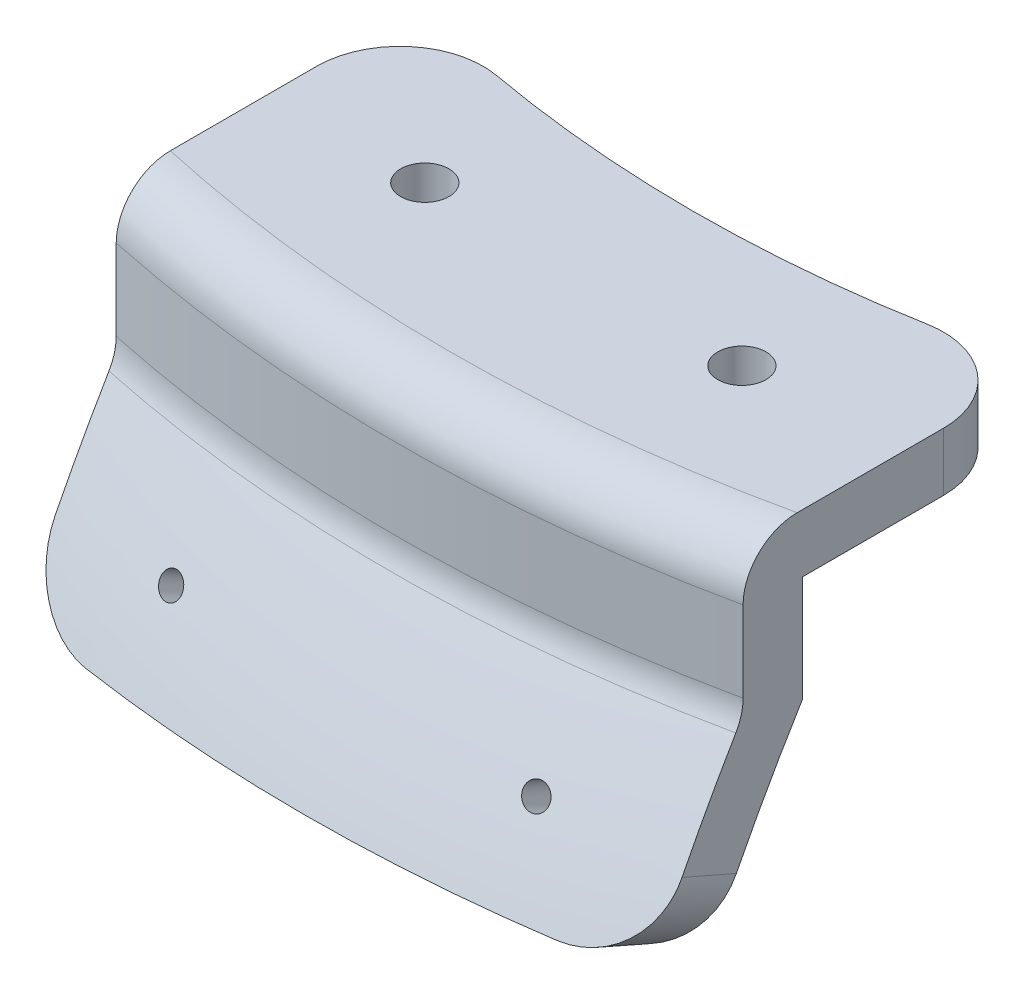
SolidWorks part; units mm, degrees
material "Polyether Polyol"
ref_plane "Front Plane" through (0, 0, 0) normal (0, 0, 1) x (1, 0, 0)
ref_plane "Top Plane" through (0, 0, 0) normal (0, 1, 0) x (1, 0, 0)
ref_plane "Right Plane" through (0, 0, 0) normal (1, 0, 0) x (0, 0, -1)
sketch "Sketch2" plane through (0, 0, 0) normal (1, 0, 0) x (0, 0, -1)
  line L0 (-174.1012, 209.4005) -> (-174.1012, 196.7005) construction
  line L1 (-192.235, 176.9476) -> (-185.8333, 174.116) construction
  line L2 (-181.1012, 216.4005) -> (-181.1012, 198.6268) construction
  line L3 (-181.1012, 216.4005) -> (-145.5262, 216.4005) construction
  line L4 (-145.5262, 216.4005) -> (-145.5262, 209.4005) construction
  line L5 (-145.5262, 209.4005) -> (-174.1012, 209.4005) construction
  line L12 (0, 91.9198) -> (0, 209.4005) construction
  line L13 (-174.1012, 209.4005) -> (-174.1012, 196.7005)
  line L14 (-192.235, 176.9476) -> (-185.8333, 174.116)
  line L15 (-181.1012, 216.4005) -> (-181.1012, 198.6268)
  line L16 (-181.1012, 216.4005) -> (-145.5262, 216.4005)
  line L17 (-145.5262, 216.4005) -> (-145.5262, 209.4005)
  line L18 (-145.5262, 209.4005) -> (-174.1012, 209.4005)
  arc A0 (-174.1012, 196.7005) -> (-185.8333, 174.116) centre (0, 91.9198) ccw construction
  arc A1 (-181.1012, 198.6268) -> (-192.235, 176.9476) centre (0, 91.9198) ccw construction
  arc A4 (-174.1012, 196.7005) -> (-185.8333, 174.116) centre (0, 91.9198) ccw
  arc A5 (-181.1012, 198.6268) -> (-192.235, 176.9476) centre (0, 91.9198) ccw
revolve "Revolve1" add sketch "Sketch2" angle 30 mid plane about L12
fillet "Fillet1" radius 6.35 2 edges at (0, 198.6268, 181.1012) (0, 216.4005, 181.1012)
sketch "Sketch3" plane through (0, 216.4005, 0) normal (0, -1, 0) x (1, 0, 0)
  circle A2 centre (-19.05, 158.6742) radius 3.5719 construction
  circle A3 centre (19.05, 158.6742) radius 3.5719 construction
  circle A4 centre (19.05, 158.6742) radius 2.9
  circle A5 centre (-19.05, 158.6742) radius 2.9
  dimension "D1" = 5.8
extrude "Cut-Extrude1" cut sketch "Sketch3" along normal through all contours A4 | A5 region at (19.05, 216.4005, 158.6742) region at (-19.05, 216.4005, 158.6742)
sketch "Sketch4" plane through (0, 216.4005, 0) normal (0, 1, 0) x (1, 0, 0)
  line L0 (37.665, -140.5675) -> (45.2289, -168.7967) construction
  line L1 (37.665, -140.5675) -> (-37.665, -140.5675)
  line L2 (37.665, -140.5675) -> (37.665, -192.235)
  line L3 (37.665, -192.235) -> (-37.665, -192.235)
  line L4 (-37.665, -140.5675) -> (-37.665, -192.235)
  line L5 (-37.665, -140.5675) -> (-45.2289, -168.7967) construction
  arc A0 (-37.665, -140.5675) -> (37.665, -140.5675) centre (0, 0) ccw construction
  arc A1 (-49.7541, -185.6848) -> (49.7541, -185.6848) centre (0, 0) ccw construction
extrude "Cut-Extrude2" cut sketch "Sketch4" against normal through all flip side to cut
fillet "Fillet2" radius 10 4 edges at (-37.665, 212.9005, 140.5675) (37.665, 212.9005, 140.5675)
sketch "Sketch5" plane through (0, 0, 0) normal (-1, 0, 0) x (0, 0, 1)
  line L0 (0, 91.9198) -> (181.0525, 184.1706) construction
  line L2 (0, -200000) -> (0, 218797.9879) construction
  arc A0 (185.8333, 174.116) -> (174.1012, 196.7005) centre (0, 91.9198) ccw construction
  dimension "D1" = 63
ref_plane "Plane1" through (0, 72.9744, -37.1823) normal (0, 0.891, -0.454) x (0, 0.454, 0.891)
sketch "Sketch6" plane through (0, 72.9744, -37.1823) normal (0, 0.891, -0.454) x (0, 0.454, 0.891)
  line L0 (217.8481, 19.0592) -> (275.7942, 24.1289) construction
  line L2 (217.8481, 19.0592) -> (275.7942, 24.1289)
  line L3 (217.8481, 19.0592) -> (217.7174, 20.5535)
  line L4 (275.7942, 24.1289) -> (275.6635, 25.6232)
  line L5 (217.7174, 20.5535) -> (275.6635, 25.6232)
  line L6 (41.7307, 0) -> (244.9307, 0) construction
  ellipse E0 centre (89.3002, 0) end of major axis (89.3002, 145.5262) minor radius 129.6648 construction
  dimension "D1" = 5
  dimension "D2" = 1.5
revolve "Cut-Revolve1" cut sketch "Sketch6" angle 360 about L0
mirror "Mirror1" about plane through (0, 0, 0) normal (1, 0, 0) of "Cut-Revolve1"
